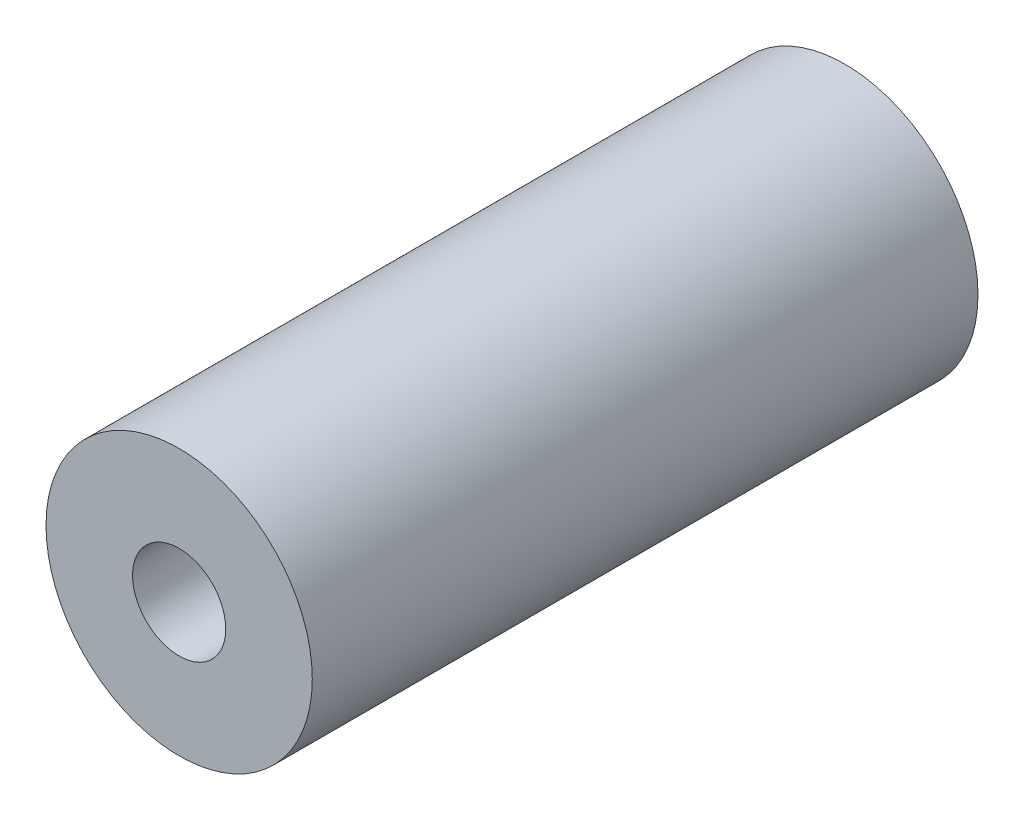
SolidWorks part; units mm, degrees
ref_plane "Front Plane" through (0, 0, 0) normal (0, 0, 1) x (1, 0, 0)
ref_plane "Top Plane" through (0, 0, 0) normal (0, 1, 0) x (1, 0, 0)
ref_plane "Right Plane" through (0, 0, 0) normal (1, 0, 0) x (0, 0, -1)
sketch "Sketch1" plane through (0, 0, 0) normal (0, 0, 1) x (1, 0, 0)
  circle A0 centre (0, 0) radius 2.1
  circle A1 centre (0, 0) radius 6
  dimension "D1" = 4.2
  dimension "D2" = 12
extrude "Boss-Extrude1" add sketch "Sketch1" along normal blind 30
